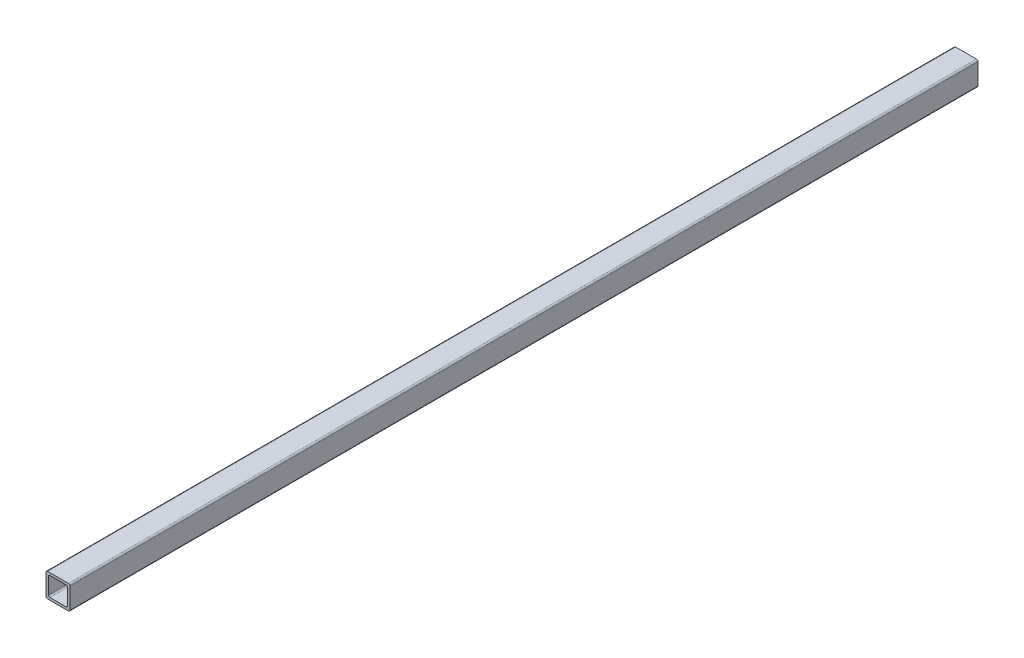
SolidWorks part; units mm, degrees
material "Hexcel AS4C (3000 Filaments)"
ref_plane "Front Plane" through (0, 0, 0) normal (0, 0, 1) x (1, 0, 0)
ref_plane "Top Plane" through (0, 0, 0) normal (0, 1, 0) x (1, 0, 0)
ref_plane "Right Plane" through (0, 0, 0) normal (1, 0, 0) x (0, 0, -1)
sketch "Sketch1" plane through (0, 0, 0) normal (0, 0, 1) x (1, 0, 0)
  line L1 (3.15, -3.15) -> (-3.15, -3.15)
  line L2 (3.15, -3.15) -> (3.15, 3.15)
  line L3 (3.15, 3.15) -> (-3.15, 3.15)
  line L4 (-3.15, -3.15) -> (-3.15, 3.15)
  line L5 (3.15, -3.15) -> (-3.15, 3.15) construction
  line L6 (3.15, 3.15) -> (-3.15, -3.15) construction
  line L7 (3.95, -3.95) -> (-3.95, -3.95)
  line L8 (3.95, -3.95) -> (3.95, 3.95)
  line L9 (3.95, 3.95) -> (-3.95, 3.95)
  line L10 (-3.95, -3.95) -> (-3.95, 3.95)
  line L11 (3.95, -3.95) -> (-3.95, 3.95) construction
  line L12 (3.95, 3.95) -> (-3.95, -3.95) construction
  point P0 (0, 0)
  point P6 (0, 0)
  dimension "D1" = 7.9
  dimension "D2" = 0.8
extrude "Boss-Extrude1" add sketch "Sketch1" along normal blind 300
fillet "Fillet1" radius 0.5 8 edges at (3.95, 3.95, 150) (3.15, 3.15, 150) (3.95, -3.95, 150) (3.15, -3.15, 150) (-3.15, -3.15, 150) (-3.95, -3.95, 150) (-3.95, 3.95, 150) (-3.15, 3.15, 150)
